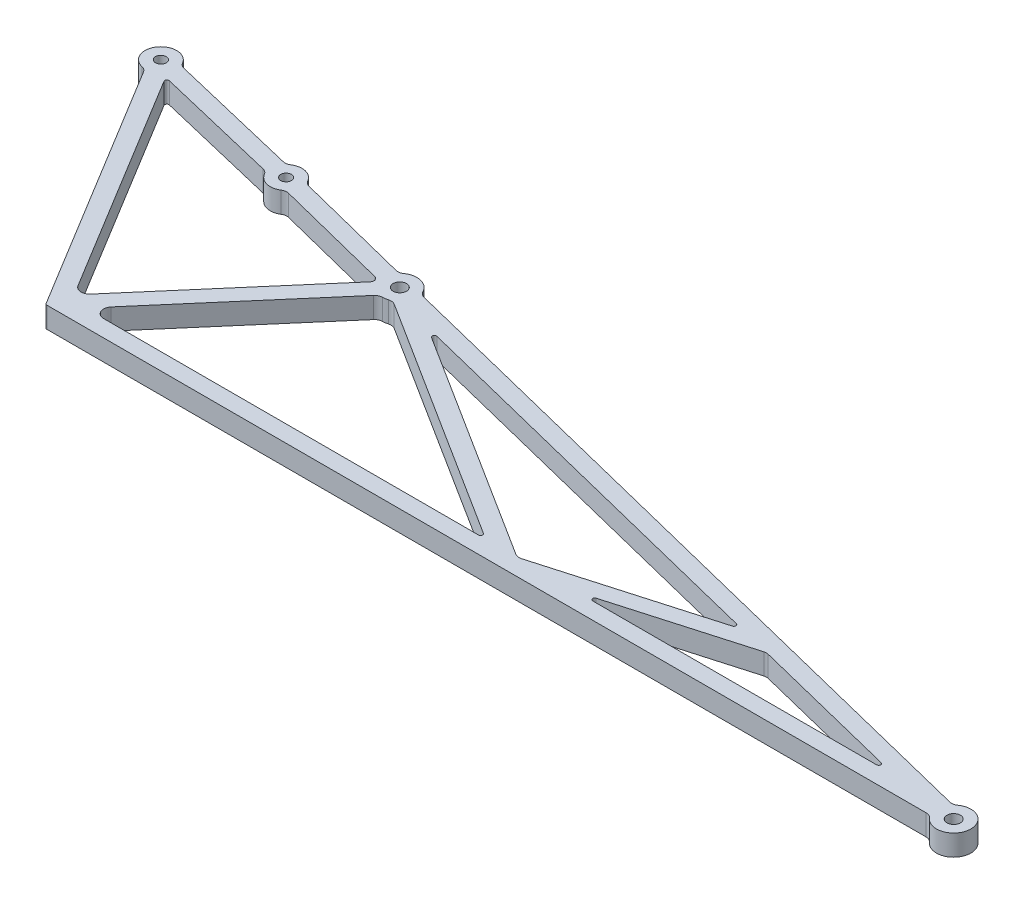
SolidWorks part; units mm, degrees
material "6061-T6 (SS)"
ref_plane "Front Plane" through (0, 0, 0) normal (0, 0, 1) x (1, 0, 0)
ref_plane "Top Plane" through (0, 0, 0) normal (0, 1, 0) x (1, 0, 0)
ref_plane "Right Plane" through (0, 0, 0) normal (1, 0, 0) x (0, 0, -1)
sketch "Sketch1" plane through (0, 0, 0) normal (0, 1, 0) x (1, 0, 0)
  line L0 (-30.2286, -999.6933) -> (-477.1134, -888.4975)
  line L1 (-477.1672, -888.4843) -> (-569.4779, -866.0351)
  line L2 (-569.5127, -866.0267) -> (-669.2968, -842.1529)
  line L4 (-32.7432, -1020.2132) -> (-580.0236, -1020.2132)
  line L5 (-580.0236, -1020.2132) -> (-679.7444, -856.5042)
  circle A0 centre (-671.5338, -851.5029) radius 3.2639 construction
  circle A1 centre (-571.7497, -875.3767) radius 3.2639 construction
  circle A2 centre (-479.628, -898.6033) radius 4.064 construction
  circle A3 centre (-32.7432, -1009.7992) radius 4.064 construction
  circle A4 centre (-671.5338, -851.5029) radius 3.2639
  circle A5 centre (-571.7497, -875.3767) radius 3.2639
  circle A6 centre (-479.628, -898.6033) radius 4.064
  circle A7 centre (-32.7432, -1009.7992) radius 4.064
  circle A8 centre (-671.5338, -851.5029) radius 9.6139
  circle A9 centre (-571.7497, -875.3767) radius 9.6139
  circle A10 centre (-479.628, -898.6033) radius 10.414
  circle A11 centre (-32.7432, -1009.7992) radius 10.414
  dimension "D2" = 152.4
  dimension "D1" = 6.35
extrude "Boss-Extrude1" add sketch "Sketch1" along normal mid plane 12.7 contours A11 L0 A10 L1 A9 L2 A8 L5 L4 | A11 A7 | A10 A6 | A9 A5 | A8 A4 | A4
sketch "Sketch2" plane through (0, 6.35, 0) normal (0, 1, 0) x (1, 0, 0)
  line L0 (-32.7432, -1009.7992) -> (-479.628, -898.6033) construction
  line L1 (-479.628, -898.6033) -> (-571.7497, -875.3767) construction
  line L2 (-571.7497, -875.3767) -> (-671.5338, -851.5029) construction
  line L3 (-32.7432, -1009.7992) -> (-575.11, -1009.7992) construction
  line L4 (-575.11, -1009.7992) -> (-671.5338, -851.5029) construction
  line L5 (-580.0236, -1020.2132) -> (-32.7432, -1020.2132)
  line L6 (-30.2286, -999.6933) -> (-477.1134, -888.4975)
  line L7 (-477.1672, -888.4843) -> (-569.4779, -866.0351)
  line L8 (-569.5127, -866.0267) -> (-669.2968, -842.1529)
  line L9 (-679.7444, -856.5042) -> (-580.0236, -1020.2132)
  line L10 (-580.0236, -1020.2132) -> (-32.7432, -1020.2132)
  line L11 (-30.2286, -999.6933) -> (-477.1134, -888.4975)
  line L12 (-477.1672, -888.4843) -> (-569.4779, -866.0351)
  line L13 (-569.5127, -866.0267) -> (-669.2968, -842.1529)
  line L14 (-679.7444, -856.5042) -> (-580.0236, -1020.2132)
  line L15 (-479.628, -898.6033) -> (-575.11, -1009.7992) construction
  line L16 (-479.628, -898.6033) -> (-303.2436, -1010.2314) construction
  line L17 (-303.2436, -1010.2314) -> (-176.8839, -973.9335) construction
  line L18 (-41.8341, -1014.8792) -> (-577.9639, -1014.8792)
  line L19 (-40.3385, -1002.6744) -> (-469.5795, -895.8688)
  line L20 (-480.87, -903.5292) -> (-572.9618, -880.3101) construction
  line L21 (-265.655, -1004.7192) -> (-176.7896, -979.1918)
  line L22 (-474.6629, -907.7575) -> (-321.4529, -1004.7192)
  line L24 (-580.8699, -878.4181) -> (-660.8462, -859.2833)
  line L25 (-489.685, -901.3066) -> (-565.0772, -882.2981)
  line L26 (-74.1977, -1004.7192) -> (-564.0521, -1004.7192)
  line L27 (-74.1977, -1004.7192) -> (-472.0327, -905.7281)
  line L28 (-450.3429, -911.1251) -> (-302.4542, -1004.7192)
  line L29 (-302.4542, -1004.7192) -> (-196.5083, -974.2853)
  line L30 (-487.2011, -891.455) -> (-562.5933, -872.4464)
  line L31 (-577.9639, -1014.8792) -> (-671.6262, -861.1163)
  line L32 (-578.5058, -868.5369) -> (-662.4136, -848.4616)
  line L33 (-478.3861, -893.6775) -> (-478.3937, -893.6756)
  line L34 (8.7113, -1014.8792) -> (-575.11, -1014.8792) construction
  line L35 (8.7113, -1014.8792) -> (-478.4014, -893.6736) construction
  line L36 (-304.0331, -1015.7436) -> (-175.4813, -978.816) construction
  line L37 (-482.3447, -902.8959) -> (-304.0331, -1015.7436) construction
  line L38 (-476.9114, -894.3108) -> (-302.4542, -1004.7192) construction
  line L39 (-302.4542, -1004.7192) -> (-178.2864, -969.0509) construction
  line L40 (-478.3861, -893.6775) -> (-570.5377, -870.4434) construction
  line L41 (-489.4045, -902.191) -> (-574.409, -1001.185)
  line L42 (-478.3937, -893.6756) -> (-478.4014, -893.6736)
  line L43 (-74.1977, -1004.7192) -> (-480.8546, -903.533) construction
  line L44 (-481.6964, -908.8099) -> (-564.0521, -1004.7192)
  line L45 (-572.9618, -880.3101) -> (-660.8462, -859.2833) construction
  line L46 (-570.5377, -870.4434) -> (-682.2214, -843.7225) construction
  line L48 (-579.4485, -1012.4419) -> (-682.2214, -843.7225) construction
  line L50 (-74.1977, -1004.7192) -> (-575.11, -1004.7192) construction
  line L51 (-574.409, -1001.185) -> (-660.8462, -859.2833)
  line L52 (-570.7715, -1007.1565) -> (-660.8462, -859.2833) construction
  circle A0 centre (-671.5338, -851.5029) radius 3.2639 construction
  circle A1 centre (-571.7497, -875.3767) radius 3.2639 construction
  circle A2 centre (-32.7432, -1009.7992) radius 4.064 construction
  circle A3 centre (-479.628, -898.6033) radius 4.064 construction
  circle A4 centre (-671.5338, -851.5029) radius 3.2639
  circle A5 centre (-571.7497, -875.3767) radius 3.2639
  circle A6 centre (-32.7432, -1009.7992) radius 4.064
  circle A7 centre (-479.628, -898.6033) radius 4.064
  circle A8 centre (-32.7432, -1009.7992) radius 10.414
  circle A9 centre (-479.628, -898.6033) radius 10.414
  circle A10 centre (-571.7497, -875.3767) radius 9.6139
  circle A11 centre (-671.5338, -851.5029) radius 9.6139
  arc A12 (-32.7432, -1020.2132) -> (-30.2286, -999.6933) centre (-32.7432, -1009.7992) ccw
  arc A13 (-477.1134, -888.4975) -> (-477.1672, -888.4843) centre (-479.628, -898.6033) ccw
  arc A14 (-569.4779, -866.0351) -> (-569.5127, -866.0267) centre (-571.7497, -875.3767) ccw
  arc A15 (-669.2968, -842.1529) -> (-679.7444, -856.5042) centre (-671.5338, -851.5029) ccw
  arc A16 (-32.7432, -1020.2132) -> (-30.2286, -999.6933) centre (-32.7432, -1009.7992) ccw
  arc A17 (-477.1134, -888.4975) -> (-477.1672, -888.4843) centre (-479.628, -898.6033) ccw
  arc A18 (-569.4779, -866.0351) -> (-569.5127, -866.0267) centre (-571.7497, -875.3767) ccw
  arc A19 (-669.2968, -842.1529) -> (-679.7444, -856.5042) centre (-671.5338, -851.5029) ccw
  line M24 (-580.0236, -1020.2132) -> (-32.7432, -1020.2132)
  line M26 (-30.2286, -999.6933) -> (-477.1134, -888.4975)
  line M28 (-477.1672, -888.4843) -> (-569.4779, -866.0351)
  line M30 (-569.5127, -866.0267) -> (-669.2968, -842.1529)
  line M32 (-679.7444, -856.5042) -> (-580.0236, -1020.2132)
  dimension "D3" = 30
  dimension "D1" = 0
  dimension "D2" = 6.35
  dimension "D4" = 5.08
  dimension "D5" = 5.08
extrude "Cut-Extrude1" cut sketch "Sketch2" against normal through all contours A10 L24 L51 L41 A9 L25 | A11 L32 A10 M30 | A10 L30 A9 M28 | A9 L19 A8 M26 | A9 L44 L26 L22 | L28 L29 L27 | L26 L27 L21 | A11 A8 L18 L31 M32 M24 | L13 A19 L14 L10 A16 L11 A17 L12 A18
fillet "Fillet1" radius 5.08 16 edges at (-662.4136, 0, 848.4616) (-578.5058, 0, 868.5369) (-671.6262, 0, 861.1163) (-41.8341, 0, 1014.8792) (-302.4542, 0, 1004.7192) (-176.7896, 0, 979.1918) (-580.8699, 0, 878.4181) (-565.0772, 0, 882.2981) (-574.409, 0, 1001.185) (-469.5795, 0, 895.8688) (-40.3385, 0, 1002.6744) (-481.6964, 0, 908.8099) (-474.6629, 0, 907.7575) (-564.0521, 0, 1004.7192) (-562.5933, 0, 872.4464) (-487.2011, 0, 891.455)
fillet "Fillet2" radius 1.27 7 edges at (-321.4529, 0, 1004.7192) (-577.9639, 0, 1014.8792) (-660.8462, 0, 859.2833) (-450.3429, 0, 911.1251) (-196.5083, 0, 974.2853) (-265.655, 0, 1004.7192) (-74.1977, 0, 1004.7192)
fillet "Fillet3" radius 2.54 4 edges at (-489.5546, 6.35, 901.7519) (-489.685, 0, 901.3066) (-489.4045, 0, 902.191) (-489.5546, -6.35, 901.7519)
